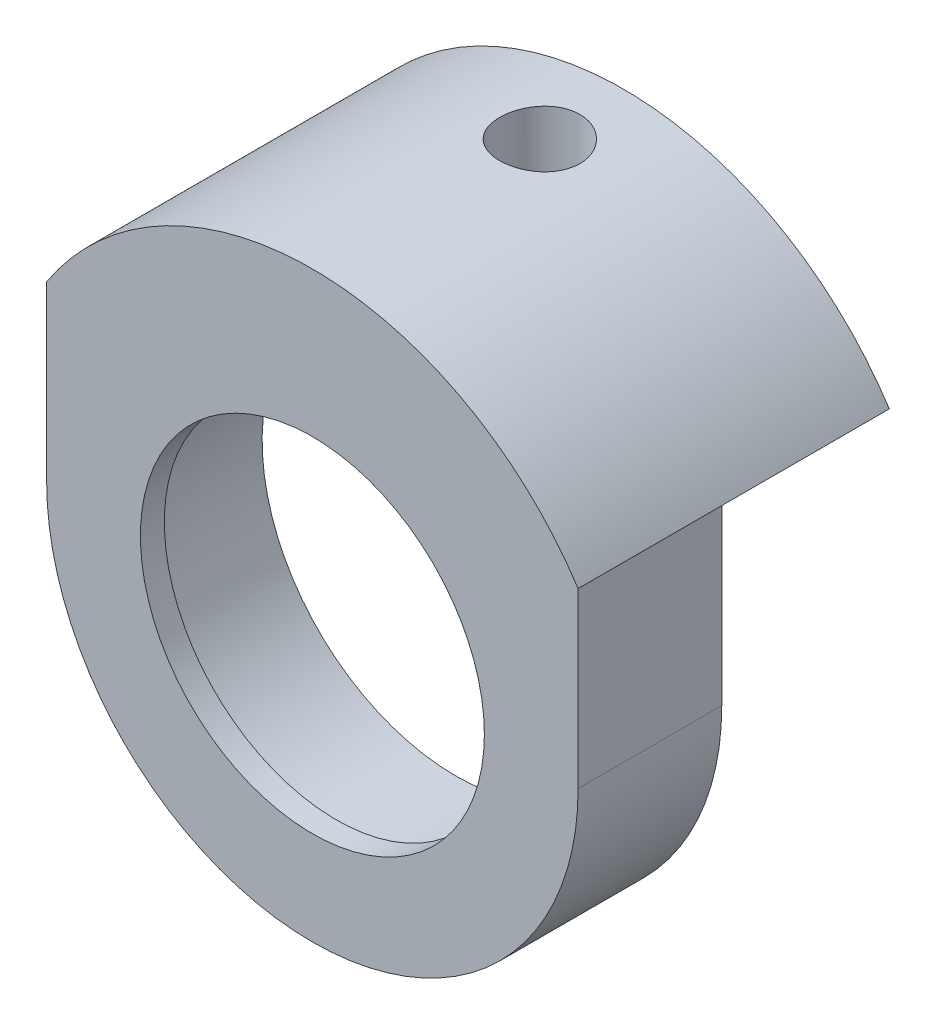
SolidWorks part; units mm, degrees
ref_plane "Front Plane" through (0, 0, 0) normal (0, 0, 1) x (1, 0, 0)
ref_plane "Top Plane" through (0, 0, 0) normal (0, 1, 0) x (1, 0, 0)
ref_plane "Right Plane" through (0, 0, 0) normal (1, 0, 0) x (0, 0, -1)
sketch "Sketch1" plane through (0, 0, 0) normal (0, 0, 1) x (1, 0, 0)
  line L0 (-11.1, 0) -> (11.1, 0)
  line L1 (-11.1, 0) -> (-11.1, 7.2355)
  line L2 (11.1, 0) -> (11.1, 7.2355)
  circle A0 centre (0, 0) radius 8.1
  circle A1 centre (0, 0) radius 13.25
  circle A2 centre (0, 0) radius 11.1
  dimension "16.2" = 16.2
  dimension "D2" = 26.5
  dimension "D3" = 3
extrude "Boss-Extrude1" add sketch "Sketch1" along normal blind 13 contours L0 A2 A0 | A2 L2 A1 L1 | L0 A2 A0 region at (0, 8.3482, 0) region at (9.6, -0.2482, 0) region at (0, 11.3585, 0)
sketch "Sketch2" plane through (-11.1, 0, 0) normal (-1, 0, 0) x (0, 0, 1)
  line L0 (13, 0) -> (13, 7.2355) construction
  line L1 (0, 7.2355) -> (7, 7.2355)
  line L2 (0, 7.2355) -> (0, -11.1)
  line L3 (0, -11.1) -> (7, -11.1)
  line L4 (7, 7.2355) -> (7, -11.1)
  dimension "D1" = 6
extrude "Cut-Extrude1" cut sketch "Sketch2" against normal up to surface (22.2 mm away) up to face at (11.1, 3.6178, 6.5)
sketch "Sketch3" plane through (0, 7.2355, 0) normal (0, -1, 0) x (1, 0, 0)
  line L0 (-3.6411, 0) -> (3.6411, 0) construction
  circle A0 centre (0, 3.5) radius 1.675
  dimension "D1" = 3.35
  dimension "D2" = 3.5
extrude "Cut-Extrude2" cut sketch "Sketch3" against normal up to surface (5.9082 mm away) up to face at (0, 9.2403, 6.6667)
sketch "Sketch4" plane through (0, 7.2355, 0) normal (0, -1, 0) x (1, 0, 0)
  line L1 (2.8, 5.1166) -> (0, 6.7332)
  line L2 (0, 6.7332) -> (-2.8, 5.1166)
  line L3 (-2.8, 5.1166) -> (-2.8, 1.8834)
  line L4 (-2.8, 1.8834) -> (0, 0.2668)
  line L5 (0, 0.2668) -> (2.8, 1.8834)
  line L6 (2.8, 1.8834) -> (2.8, 5.1166)
  line L7 (-3.6411, 0) -> (-3.6411, 7) construction
  circle A0 centre (0, 3.5) radius 2.8 construction
  dimension "5.55" = 5.6
extrude "Cut-Extrude3" cut sketch "Sketch4" against normal blind 3
sketch "Sketch5" plane through (0, 0, 13) normal (0, 0, 1) x (1, 0, 0)
  circle A0 centre (0, 0) radius 8.1835
  circle A1 centre (0, 0) radius 7.1835
  dimension "D1" = 1
extrude "Boss-Extrude2" add sketch "Sketch5" against normal blind 1
